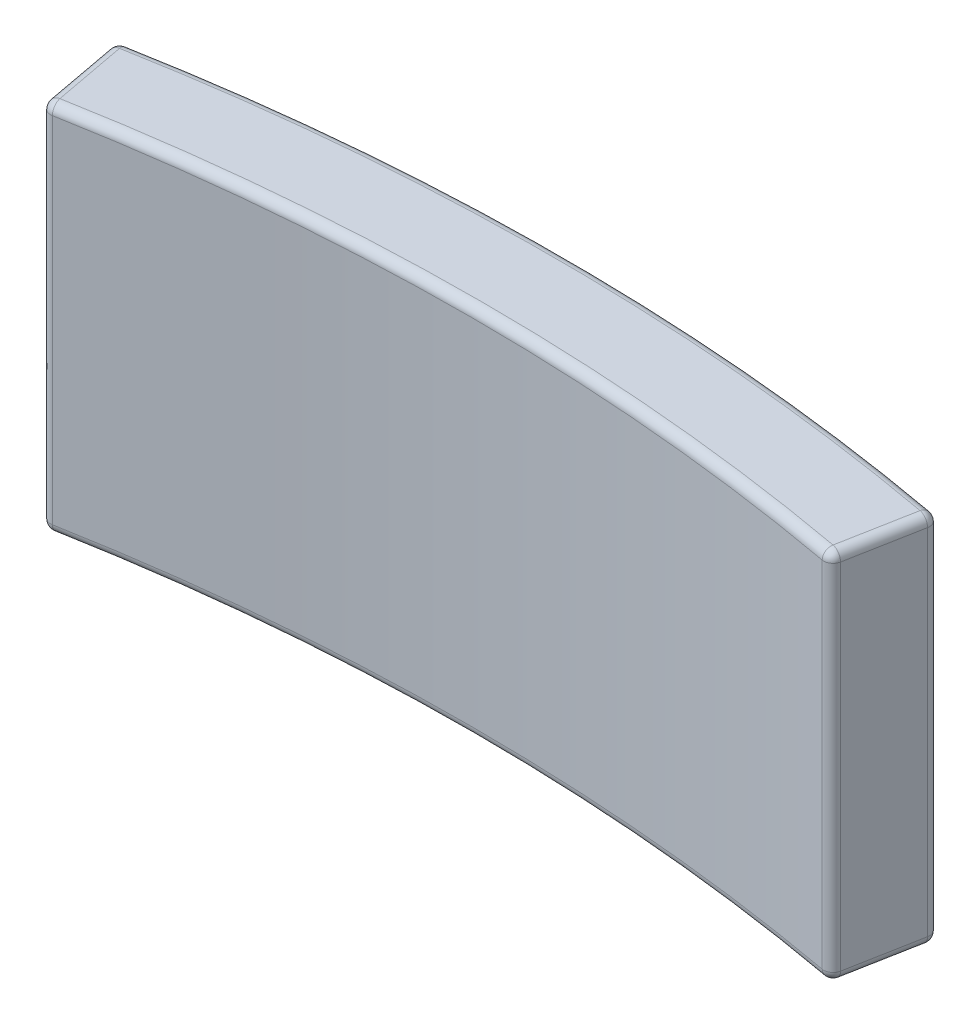
SolidWorks part; units mm, degrees
material "Ductile Iron"
ref_plane "Front Plane" through (0, 0, 0) normal (0, 0, 1) x (1, 0, 0)
ref_plane "Top Plane" through (0, 0, 0) normal (0, 1, 0) x (1, 0, 0)
ref_plane "Right Plane" through (0, 0, 0) normal (1, 0, 0) x (0, 0, -1)
ref_axis "CentralAxis" through (0, 2.2, 0) along (0, -1, 0)
sketch "ProfileS" plane through (0, 0, 0) normal (0, 1, 0) x (1, 0, 0)
  line L0 (4.2262, 22.6084) -> (4.41, 23.5914)
  line L1 (-4.2262, 22.6084) -> (-4.41, 23.5914)
  line L2 (0, 0) -> (0, 24) construction
  line L3 (0, 0) -> (-4.2262, 22.6084) construction
  arc A0 (4.2262, 22.6084) -> (-4.2262, 22.6084) centre (0, 0) ccw
  arc A1 (4.41, 23.5914) -> (-4.41, 23.5914) centre (0, 0) ccw
  dimension "Diameter" = 48
  dimension "Thickness" = 1
  dimension "ArcAngle" = 21.176
extrude "Profile" add sketch "ProfileS" along normal mid plane 4
fillet "ProfileFillet" radius 0.1 12 edges at (0, -2, -23) (-4.2262, 0, -22.6084) (-4.3181, -2, -23.0999) (4.2262, 0, -22.6084) (4.3181, -2, -23.0999) (4.3181, 2, -23.0999) (0, 2, -23) (-4.3181, 2, -23.0999) (4.41, 0, -23.5914) (0, 2, -24) (-4.41, 0, -23.5914) (0, -2, -24)
